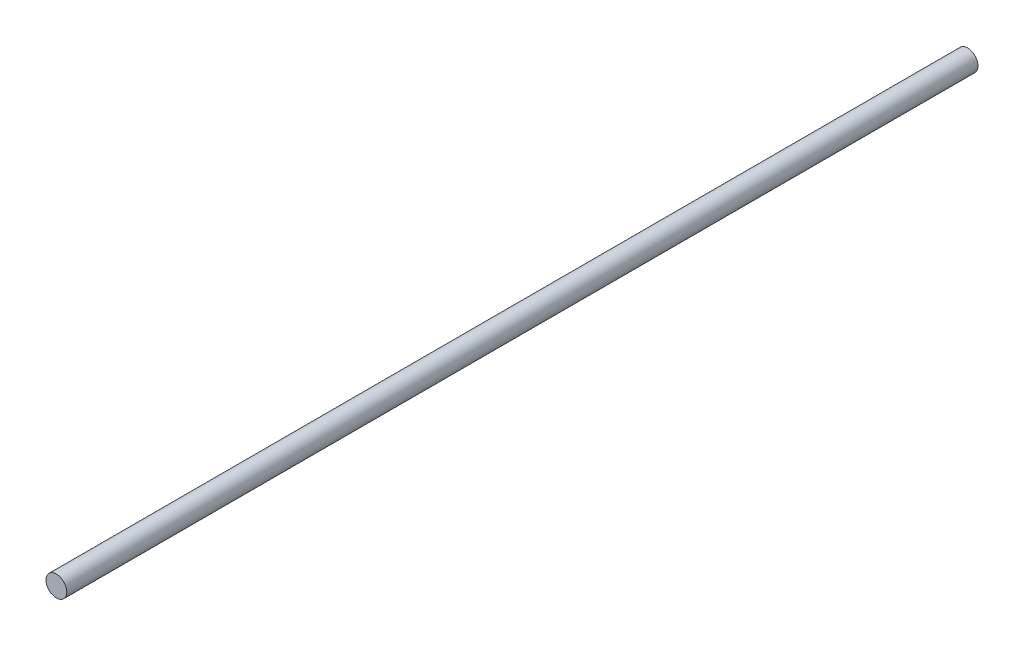
SolidWorks part; units mm, degrees
material "AISI 316 Stainless Steel Sheet (SS)"
ref_plane "Front (1)" through (0, 0, 0) normal (0, 0, 1) x (1, 0, 0)
ref_plane "Top (2)" through (0, 0, 0) normal (0, 1, 0) x (1, 0, 0)
ref_plane "Right (3)" through (0, 0, 0) normal (1, 0, 0) x (0, 0, -1)
ref_axis "X Axis" through (13.5064, 0, 0) along (-1, 0, 0)
ref_axis "Y Axis" through (0, 12.3593, 0) along (0, -1, 0)
ref_axis "Z Axis" through (0, 0, 14.1119) along (0, 0, -1)
sketch "Sketch2" plane through (0, 0, 0) normal (1, 0, 0) x (0, 0, -1)
  line L0 (-19.1, 0) -> (0, 0) construction
  line L1 (-19.1, 0) -> (331.5, 0)
  line L2 (-19.1, 0) -> (-19.1, 4)
  line L3 (-19.1, 4) -> (331.5, 4)
  line L4 (331.5, 0) -> (331.5, 4)
  dimension "D1" = 350.6
  dimension "D2" = 4
revolve "Revolve1" add sketch "Sketch2" angle 360 about L0
cosmetic thread "Cosmetic Thread2" parameters "D2"=6.891
